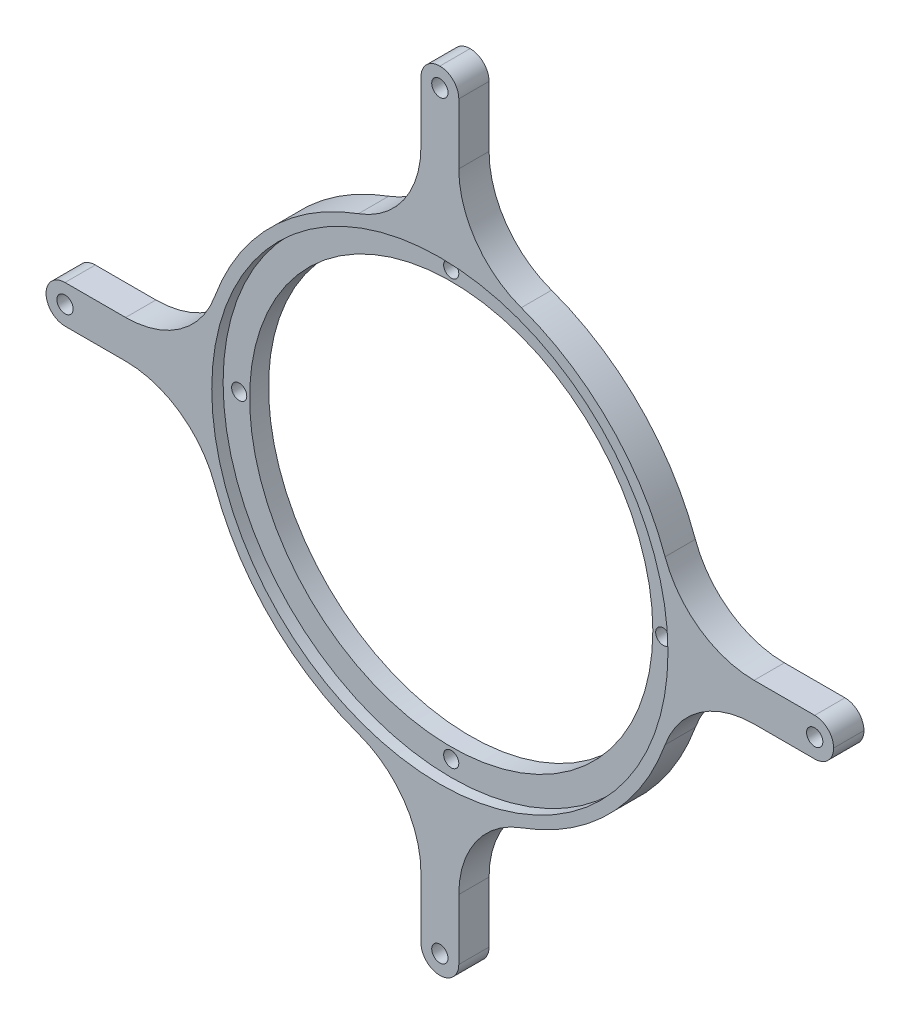
SolidWorks part; units mm, degrees
ref_plane "Alzado" through (0, 0, 0) normal (0, 0, 1) x (1, 0, 0)
ref_plane "Planta" through (0, 0, 0) normal (0, 1, 0) x (1, 0, 0)
ref_plane "Vista lateral" through (0, 0, 0) normal (1, 0, 0) x (0, 0, -1)
sketch "Croquis1" plane through (0, 0, 0) normal (0, 0, 1) x (1, 0, 0)
  circle A0 centre (0, 0) radius 60.25
  circle A2 centre (0, 56) radius 2
  circle A3 centre (0, 0) radius 53.25
  circle A4 centre (56, 0) radius 2
  circle A5 centre (0, -56) radius 2
  circle A6 centre (-56, 0) radius 2
  point P15 (0, 0)
  dimension "D1" = 120.5
  dimension "D2" = 56
  dimension "D3" = 4
  dimension "D4" = 7
  dimension "D5" = 4
extrude "Saliente-Extruir1" add sketch "Croquis1" along normal blind 5
extrude "Extruir-Lámina1" add sketch "Croquis1<2>" along normal blind 8 thin contours A0 thin type one direction wall 3
sketch "Croquis1<2>" plane through (0, 0, 0) normal (0, 0, 1) x (1, 0, 0) same geometry as "Croquis1"
sketch "Croquis2" plane through (0, 0, 0) normal (0, 0, 1) x (1, 0, 0)
  line L1 (-5, 63.0521) -> (5, 63.0521)
  line L2 (-5, 63.0521) -> (-5, 104)
  line L3 (-5, 104) -> (5, 104)
  line L4 (5, 63.0521) -> (5, 104)
  line L5 (63.0521, 5) -> (104, 5)
  line L6 (63.0521, 5) -> (63.0521, -5)
  line L7 (63.0521, -5) -> (104, -5)
  line L8 (104, 5) -> (104, -5)
  line L9 (5, -63.0521) -> (5, -104)
  line L10 (5, -63.0521) -> (-5, -63.0521)
  line L11 (-5, -63.0521) -> (-5, -104)
  line L12 (5, -104) -> (-5, -104)
  line L13 (-63.0521, -5) -> (-104, -5)
  line L14 (-63.0521, -5) -> (-63.0521, 5)
  line L15 (-63.0521, 5) -> (-104, 5)
  line L16 (-104, -5) -> (-104, 5)
  circle A0 centre (0, 0) radius 63.25 construction
  circle A1 centre (0, 99) radius 1.25
  circle A2 centre (99, 0) radius 1.25
  circle A3 centre (0, -99) radius 1.25
  circle A4 centre (-99, 0) radius 1.25
  point P6 (0, 104)
  point P31 (0, 0)
  point P33 (63.0521, 0)
  dimension "D2" = 2.5
  dimension "D1" = 10
  dimension "D3" = 5
  dimension "D4" = 4
  dimension "D5" = 198
extrude "Saliente-Extruir2" add sketch "Croquis2" along normal blind 8
fillet "Redondeo1" radius 25 8 edges at (-5, 63.0521, 4) (-63.0521, 5, 4) (-63.0521, -5, 4) (-5, -63.0521, 4) (5, -63.0521, 4) (63.0521, -5, 4) (63.0521, 5, 4) (5, 63.0521, 4)
sketch "Croquis3" plane through (0, 0, 8) normal (0, 0, 1) x (1, 0, 0)
  circle A0 centre (0, 99) radius 2.15
  circle A1 centre (99, 0) radius 2.15
  circle A2 centre (0, -99) radius 2.15
  circle A3 centre (-99, 0) radius 2.15
  point P12 (0, 0)
  dimension "D1" = 4.3
  dimension "D2" = 4
extrude "Cortar-Extruir1" cut sketch "Croquis3" against normal blind 5
fillet "Redondeo2" radius 5 8 edges at (-104, -5, 4) (-104, 5, 4) (-5, -104, 4) (5, -104, 4) (104, -5, 4) (104, 5, 4) (5, 104, 4) (-5, 104, 4)
